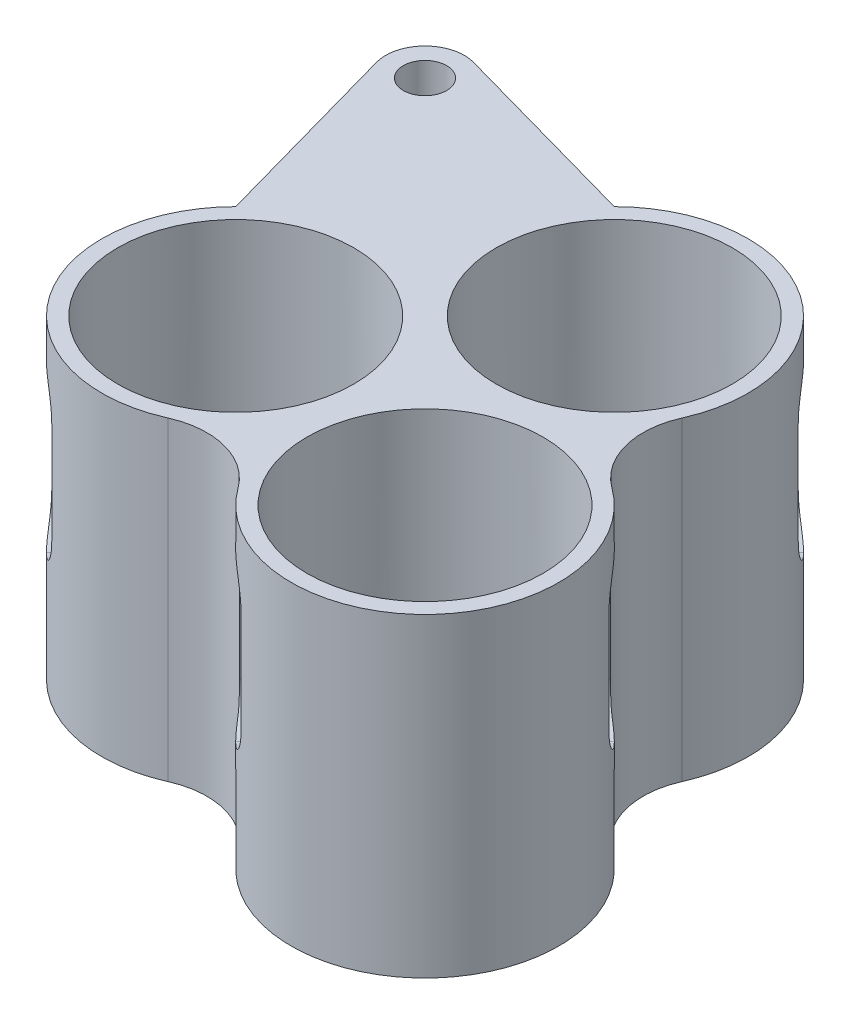
SolidWorks part; units mm, degrees
ref_plane "Front Plane" through (0, 0, 0) normal (0, 0, 1) x (1, 0, 0)
ref_plane "Top Plane" through (0, 0, 0) normal (0, 1, 0) x (1, 0, 0)
ref_plane "Right Plane" through (0, 0, 0) normal (1, 0, 0) x (0, 0, -1)
sketch "Sketch1" plane through (0, 0, 0) normal (0, 1, 0) x (1, 0, 0)
  line L1 (-15, -15) -> (15, -15)
  line L2 (-15, -15) -> (-15, 15)
  line L3 (-15, 15) -> (15, 15)
  line L4 (15, -15) -> (15, 15)
  line L5 (-15, -15) -> (15, 15) construction
  line L6 (-15, 15) -> (15, -15) construction
  point P0 (0, 0)
  dimension "D1" = 30
extrude "Boss-Extrude1" add sketch "Sketch1" along normal blind 80
sketch "Sketch2" plane through (0, 80, 0) normal (0, 1, 0) x (1, 0, 0)
  line L0 (-15, -15) -> (15, -15) construction
  line L1 (15, -15) -> (15, 15) construction
  circle A0 centre (9, -9) radius 6
  dimension "D1" = 12
extrude "Boss-Extrude2" add sketch "Sketch2" along normal blind 22
sketch "Sketch3" plane through (0, 80, 0) normal (0, 1, 0) x (1, 0, 0)
  line L2 (9, -15) -> (15, -15)
  line L4 (15, -15) -> (15, -9)
  circle A1 centre (9, -9) radius 6
  arc A4 (9, -15) -> (15, -9) centre (9, -9) ccw
  dimension "D1" = 0
extrude "Cut-Extrude1" cut sketch "Sketch3" against normal through all
sketch "Sketch4" plane through (0, 80, 0) normal (0, 1, 0) x (1, 0, 0)
  line L1 (-8.25, 11.25) -> (-1.75, 11.25) construction
  line L2 (-8.25, 11.25) -> (-8.25, 8.25)
  line L6 (-1.75, 1.75) -> (-11.25, 1.75)
  line L8 (-8.25, 8.25) -> (-11.25, 8.25)
  line L9 (-11.25, 1.75) -> (-11.25, 8.25) construction
  line L10 (-1.75, 11.25) -> (-1.75, 1.75)
  line L11 (-11.25, -1.25) -> (1.25, -1.25)
  line L12 (1.25, -1.25) -> (1.25, 11.25)
  line L13 (1.25, 11.25) -> (-1.75, 11.25) construction
  line L14 (-11.25, 1.75) -> (-11.25, -1.25) construction
  line L15 (-11.25, 8.25) -> (-11.25, 11.25) construction
  line L16 (-11.25, 11.25) -> (-8.25, 11.25) construction
  line L17 (1.25, 11.25) -> (1.25, 15)
  line L18 (15, 15) -> (-15, 15) construction
  line L19 (1.25, 15) -> (-1.75, 15)
  line L20 (-1.75, 15) -> (-1.75, 11.25)
  line L21 (-8.25, 11.25) -> (-8.25, 15)
  line L22 (-8.25, 15) -> (-11.25, 15)
  line L23 (-11.25, 15) -> (-11.25, 11.25)
  line L24 (-11.25, 11.25) -> (-15, 11.25)
  line L25 (-15, 15) -> (-15, -15) construction
  line L26 (-15, 11.25) -> (-15, 8.25)
  line L27 (-15, 8.25) -> (-11.25, 8.25)
  line L28 (-11.25, 1.75) -> (-15, 1.75)
  line L29 (-15, 1.75) -> (-15, -1.25)
  line L30 (-15, -1.25) -> (-11.25, -1.25)
  dimension "D1" = 6.5
  dimension "D2" = 3
  dimension "D3" = 3.75
extrude "Boss-Extrude3" add sketch "Sketch4" along normal blind 100
sketch "Sketch6" plane through (0, 0, 0) normal (0, -1, 0) x (1, 0, 0)
  line L1 (15, -15) -> (7, -15)
  line L2 (15, -15) -> (15, -105.5)
  line L3 (15, -105.5) -> (13, -105.5)
  line L4 (7, -15) -> (7, -99.5)
  arc A1 (7, -99.5) -> (13, -105.5) centre (7, -105.5) ccw
  dimension "D3" = 12
  dimension "D1" = 90.5
  dimension "D2" = 8
extrude "Boss-Extrude5" add sketch "Sketch6" against normal blind 2
sketch "Sketch7" plane through (0, 2, 0) normal (0, 1, 0) x (1, 0, 0)
  line L0 (7, 109.5) -> (7, 111.5) construction
  line L1 (9, 111.1569) -> (9, 108.9641)
  line L2 (5, 111.1569) -> (5, 108.9641)
  line L3 (7, 101.5) -> (7, 99.5) construction
  line L4 (15, 105.5) -> (13, 105.5)
  line L5 (15, 105.5) -> (15, 15)
  line L6 (15, 15) -> (7, 15)
  line L7 (7, 15) -> (7, 99.5) construction
  line L8 (15, 15) -> (1.25, 15) construction
  line L9 (7, 15) -> (7, 99.5)
  arc A0 (5, 111.1569) -> (7, 99.5) centre (7, 105.5) ccw
  arc A1 (13, 105.5) -> (7, 99.5) centre (7, 105.5) ccw construction
  arc A2 (5, 108.9641) -> (9, 108.9641) centre (7, 105.5) ccw
  arc A3 (13, 105.5) -> (9, 111.1569) centre (7, 105.5) ccw
  dimension "D1" = 2
  dimension "D2" = 2
extrude "Boss-Extrude6" add sketch "Sketch7" along normal offset from surface (23 mm away) 25 up to face at (3.75, 0, -38.4375)
sketch "Sketch9" plane through (0, 0, 0) normal (0, -1, 0) x (1, 0, 0)
  line L0 (15, -15) -> (7, -15) construction
  line L1 (-15, 15) -> (-132.175, 15) construction
  line L2 (-15, 15) -> (-15, 7)
  line L3 (-15, 7) -> (-126.175, 7) construction
  line L4 (-132.175, 15) -> (-132.175, 13.1746) construction
  line L5 (-136.05, 7) -> (-136.175, 7) construction
  line L6 (-128.175, 7) -> (-126.175, 7) construction
  line L7 (-126.175, 9) -> (-128.856, 9) construction
  line L8 (7, -109.5) -> (7, -111.5) construction
  line L9 (9, -111.1569) -> (5, -111.1569) construction
  line L10 (-126.175, 5) -> (-128.856, 5) construction
  line L11 (-126.175, 9) -> (-126.175, 5) construction
  line L12 (-128.7978, 8.9) -> (-126.3, 8.9)
  line L13 (-128.7978, 5.1) -> (-126.175, 5.1) construction
  line L14 (-126.175, 5.1) -> (-126.175, 7) construction
  line L15 (-126.175, 8.9) -> (-126.3, 8.9) construction
  line L16 (-132.05, 15) -> (-132.05, 13.1733)
  line L17 (-132.05, 14.0867) -> (-132.175, 14.0873) construction
  line L18 (-132.05, 15) -> (-15, 15)
  line L19 (-126.175, 5.1) -> (-126.175, 7) construction
  line L20 (-15, 7) -> (-126.175, 7)
  line L21 (-126.4838, 5.1) -> (-128.7978, 5.1)
  circle A0 centre (-132.175, 7) radius 4 construction
  arc A1 (9, -108.9641) -> (5, -108.9641) centre (7, -105.5) ccw construction
  arc A2 (-128.7978, 8.9) -> (-128.7978, 5.1) centre (-132.175, 7) ccw
  arc A4 (-126.3, 8.9) -> (-132.175, 13.1746) centre (-132.175, 7) ccw construction
  arc A6 (-126.3, 8.9) -> (-132.05, 13.1733) centre (-132.175, 7) ccw
  arc A7 (-126.4838, 5.1) -> (-126.175, 7) centre (-132.175, 7) ccw
  arc A8 (7, -99.5) -> (5, -111.1569) centre (7, -105.5) ccw construction
  dimension "D1" = 117.175
  dimension "D2" = 0.125
  dimension "D3" = 1.9
extrude "Boss-Extrude7" add sketch "Sketch9" against normal blind 25
fillet "Fillet1" radius 2 1 edges at (-126.175, 12.5, 7)
sketch "Sketch11" plane through (0, 0, 0) normal (0, -1, 0) x (1, 0, 0)
  line L0 (-126.3, 8.9) -> (-126.425, 8.9) construction
  line L2 (-126.3, 8.9) -> (-128.7978, 8.9) construction
  line L3 (-136.05, 7) -> (-136.175, 7) construction
  circle A0 centre (-132.175, 7) radius 6.0558
  arc A5 (-128.7978, 8.9) -> (-128.7978, 5.1) centre (-132.175, 7) ccw construction
extrude "Cut-Extrude2" cut sketch "Sketch11" against normal offset from surface (2.125 mm away) 0.125 up to face at (7, 2, -108.2802) offset beyond the face yes
sketch "Sketch12" plane through (-15, 0, 0) normal (-1, 0, 0) x (0, 0, 1)
  line L1 (-15, 77) -> (-1.75, 77)
  line L2 (-15, 77) -> (-15, 68.5)
  line L3 (-15, 68.5) -> (-1.75, 68.5)
  line L4 (-1.75, 77) -> (-1.75, 68.5)
  line L6 (-15, 80) -> (-15, 0) construction
  line L7 (-15, 80) -> (-1.75, 80) construction
  line L9 (-1.75, 180) -> (-1.75, 80) construction
  dimension "D1" = 8.5
  dimension "D2" = 3
extrude "Cut-Extrude4" cut sketch "Sketch12" against normal up to surface (13.25 mm away) up to face at (-1.75, 130, -8.375)
sketch "Sketch14" plane through (0, 0, 15) normal (0, 0, 1) x (1, 0, 0)
  line L0 (15, 0) -> (-136.05, 0) construction
  line L1 (-136.05, 25) -> (-136.05, 2.125) construction
  line L2 (-132.05, 0) -> (9, 0) construction
sketch "Sketch15" plane through (0, 80, 0) normal (0, 1, 0) x (1, 0, 0)
  line L4 (-11.25, 11.25) -> (-11.25, 15)
  line L5 (-11.25, 15) -> (-15, 15)
  line L6 (-15, 15) -> (-15, 11.25)
  line L7 (-15, 11.25) -> (-11.25, 11.25)
  line L8 (-11.25, 11.25) -> (-11.25, 15)
  line L9 (-11.25, 15) -> (-15, 15)
  line L10 (-15, 15) -> (-15, 11.25)
  line L11 (-15, 11.25) -> (-11.25, 11.25)
  dimension "D1" = 0
extrude "Cut-Extrude5" cut sketch "Sketch15" against normal up to next
fillet "Fillet2" radius 1 5 edges at (1.25, 130, -15) (-11.25, 128.5, -15) (-11.25, 128.5, -11.25) (-15, 128.5, -11.25) (-15, 130, 1.25)
sketch "Sketch16" plane through (0, 80, 0) normal (0, 1, 0) x (1, 0, 0)
  circle A0 centre (9, -9) radius 6
  circle A1 centre (9, -9) radius 6 construction
extrude "Cut-Extrude7" cut sketch "Sketch16" along normal up to next
sketch "Sketch17" plane through (0, 180, 0) normal (0, 1, 0) x (1, 0, 0)
  line L0 (18.7916, -9.75) -> (18.7916, -11.75) construction
  line L1 (1.25, 5.25) -> (3.7916, 5.25) construction
  line L2 (1.25, -1.25) -> (1.25, 14) construction
  line L3 (-5.25, -3.7916) -> (-5.25, -1.25) construction
  line L4 (-14, -1.25) -> (1.25, -1.25) construction
  line L6 (-5.25, -1.25) -> (1.25, -1.25) construction
  line L7 (1.25, -1.25) -> (1.25, 5.25) construction
  line L8 (-14, -1.25) -> (-14, -4.2164)
  line L9 (1.25, 14) -> (4.2164, 14)
  line L10 (-14, -1.25) -> (1.25, -1.25)
  line L11 (1.25, -1.25) -> (1.25, 14)
  circle A0 centre (18.7916, 5.25) radius 15
  circle A1 centre (-5.25, -18.7916) radius 15
  arc A2 (20.5619, -11.6576) -> (4.2164, 14) centre (18.7916, 5.25) ccw
  arc A3 (-14, -4.2164) -> (11.6576, -20.5619) centre (-5.25, -18.7916) ccw
  arc A4 (11.6576, -20.5619) -> (20.5619, -11.6576) centre (21.6032, -21.6032) cw
  dimension "D1" = 30
  dimension "D3" = 10
  dimension "D2" = 2
  dimension "D4" = 6.5
extrude "Boss-Extrude8" add sketch "Sketch17" against normal blind 40
fillet "Fillet3" radius 1 4 edges at (4.2164, 160, -14) (1.25, 160, -14) (-14, 160, 1.25) (-14, 160, 4.2164)
sketch "Sketch18" plane through (0, 140, 0) normal (0, -1, 0) x (1, 0, 0)
  circle A0 centre (-5.25, 18.7916) radius 15 construction
  circle A1 centre (-5.25, 18.7916) radius 15
  circle A2 centre (-5.25, 18.7916) radius 7.5
  dimension "D1" = 15
extrude "Boss-Extrude9" add sketch "Sketch18" against normal blind 2
sketch "Sketch19" plane through (0, 140, 0) normal (0, -1, 0) x (1, 0, 0)
  line L0 (-5.25, 26.2916) -> (-5.25, 11.2916) construction
  circle A0 centre (-5.25, 18.7916) radius 7.5 construction
ref_plane "Plane1" through (-5.25, 0, 0) normal (-1, 0, 0) x (0, 0, -1)
sketch "Sketch21" plane through (-5.25, 0, 0) normal (-1, 0, 0) x (0, 0, -1)
  line L0 (-11.2916, -142) -> (-3.7916, -154.5)
  line L1 (-26.2916, -142) -> (-11.2916, -142) construction
  line L2 (-3.7916, -154.5) -> (-3.7916, -142)
  line L3 (-33.7916, -142) -> (-3.7916, -142) construction
  line L4 (-3.7916, -142) -> (-11.2916, -142)
  line L5 (-18.7916, -1065) -> (-18.7916, 48935) construction
  line L6 (-26.2916, -140) -> (-11.2916, -140) construction
  point P14 (-18.7916, -140)
  dimension "D1" = 12.5
revolve "Revolve1" add sketch "Sketch21" angle 360 about L5
ref_plane "Plane2" through (0, 0, 0) normal (0.7071, 0, -0.7071) x (-0.7071, 0, -0.7071)
mirror "Mirror1" about plane through (0, 0, 0) normal (0.7071, 0, -0.7071) of "Revolve1", "Boss-Extrude9"
sketch "Sketch22" plane through (0, 140, 0) normal (0, -1, 0) x (1, 0, 0)
  circle A0 centre (0, 0) radius 209.0164
extrude "Cut-Extrude8" cut sketch "Sketch22" along normal through all
sketch "Sketch23" plane through (0, 180, 0) normal (0, 1, 0) x (1, 0, 0)
  line L1 (-26.7546, 5.072) -> (-4.6842, 5.072)
  line L2 (-26.7546, 5.072) -> (-26.7546, 21.2842)
  line L3 (-26.7546, 21.2842) -> (-4.6842, 21.2842)
  line L4 (-4.6842, 5.072) -> (-4.6842, 21.2842)
extrude "Cut-Extrude9" cut sketch "Sketch23" against normal through all
sketch "Sketch24" plane through (0, 180, 0) normal (0, 1, 0) x (1, 0, 0)
  line L0 (-1.75, 1.75) -> (0, 0) construction
  line L1 (0, 0) -> (39.6123, -39.6123) construction
  line L2 (-5.25, -18.7916) -> (18.7916, 5.25) construction
  line L3 (18.7916, 5.25) -> (27.5915, -27.5915) construction
  line L4 (27.5915, -27.5915) -> (-5.25, -18.7916) construction
  line L5 (-20.25, -18.7916) -> (-22.25, -18.7916) construction
  line L6 (42.5915, -27.5915) -> (44.5915, -27.5915) construction
  circle A0 centre (27.5915, -27.5915) radius 15
  circle A1 centre (18.7916, 5.25) radius 15 construction
  circle A2 centre (18.7916, 5.25) radius 15 construction
  arc A3 (13.8342, -37.5784) -> (37.5784, -13.8342) centre (27.5915, -27.5915) ccw
  circle A4 centre (-5.25, -18.7916) radius 15 construction
  arc A5 (-14.4583, -4.5015) -> (11.6576, -20.5619) centre (-5.25, -18.7916) ccw construction
  arc A6 (13.8342, -37.5784) -> (1.6707, -34.3192) centre (5.7417, -43.453) ccw
  arc A7 (37.5784, -13.8342) -> (34.3192, -1.6707) centre (43.453, -5.7417) cw
  arc A8 (20.5619, -11.6576) -> (11.6576, -20.5619) centre (21.6032, -21.6032) ccw construction
  arc A9 (20.5619, -11.6576) -> (4.5015, 14.4583) centre (18.7916, 5.25) ccw construction
  arc A10 (20.5619, -11.6576) -> (34.3192, -1.6707) centre (18.7916, 5.25) ccw
  arc A11 (20.5619, -11.6576) -> (11.6576, -20.5619) centre (21.6032, -21.6032) ccw
  arc A12 (1.6707, -34.3192) -> (11.6576, -20.5619) centre (-5.25, -18.7916) ccw
extrude "Boss-Extrude10" add sketch "Sketch24" against normal up to surface (40 mm away) up to face at (-2.677, 140, -2.677)
sketch "Sketch25" plane through (0, 140, 0) normal (0, -1, 0) x (1, 0, 0)
  circle A0 centre (27.5915, 27.5915) radius 15 construction
  circle A1 centre (27.5915, 27.5915) radius 15
  circle A2 centre (27.5915, 27.5915) radius 7.5
  circle A3 centre (-5.25, 18.7916) radius 7.5 construction
extrude "Boss-Extrude11" add sketch "Sketch25" against normal blind 2
ref_plane "Plane3" through (0, 0, 0) normal (0.7071, 0, -0.7071) x (-0.7071, 0, -0.7071)
sketch "Sketch26" plane through (0, 0, 0) normal (0.7071, 0, -0.7071) x (-0.7071, 0, -0.7071)
  line L0 (-39.0202, 126.9954) -> (-39.0202, 195.0175) construction
  line L2 (-24.0202, 142) -> (-24.0202, 154.5)
  line L3 (-24.0202, 154.5) -> (-31.5202, 142)
  line L4 (-31.5202, 142) -> (-24.0202, 142)
  line L5 (-24.0202, 142) -> (-54.0202, 142) construction
  line L7 (-24.0202, 142) -> (-24.0202, 180) construction
  line L8 (-31.5202, 142) -> (-46.5202, 142) construction
  dimension "D1" = 12.5
revolve "Revolve2" add sketch "Sketch26" angle 360 about L0
sketch "Sketch27" plane through (0, 180, 0) normal (0, 1, 0) x (1, 0, 0)
  line L0 (2.25, 14) -> (2.25, -2.25) construction
  line L1 (2.25, -2.25) -> (-14, -2.25) construction
  line L2 (2.25, -2.25) -> (2.25, 72.75)
  line L3 (2.25, 72.75) -> (-1.75, 72.75)
  line L4 (-1.75, 72.75) -> (-1.75, 1.75)
  line L5 (-1.75, 15) -> (-1.75, 1.75) construction
  line L6 (-1.75, 1.75) -> (-72.75, 1.75)
  line L7 (-72.75, 1.75) -> (-72.75, -2.25)
  line L8 (-72.75, -2.25) -> (2.25, -2.25)
  line L9 (-1.75, 1.75) -> (-15, 1.75) construction
  line L10 (3.6609, 14) -> (1.9821, 14) construction
  line L11 (-14, -1.9821) -> (-14, -3.6609) construction
  dimension "D1" = 4
  dimension "D2" = 75
extrude "Boss-Extrude12" add sketch "Sketch27" against normal up to surface (40 mm away) up to face at (0.8594, 140, 0.8594)
sketch "Sketch29" plane through (0, 0, 2.25) normal (0, 0, 1) x (1, 0, 0)
  line L0 (-72.75, 140) -> (-14, 140) construction
  line L1 (-14, 140) -> (-14, 180) construction
  line L2 (-72.75, 160) -> (-8.9096, 160) construction
  line L3 (-72.75, 140) -> (-72.75, 180) construction
  circle A0 centre (-24, 144) radius 2
  circle A1 centre (-24, 176) radius 2
  circle A2 centre (-68.75, 144) radius 2
  circle A3 centre (-68.75, 176) radius 2
  dimension "D1" = 4
  dimension "D2" = 4
  dimension "D3" = 10
  dimension "D4" = 4
extrude "Cut-Extrude10" cut sketch "Sketch29" against normal through all
sketch "Sketch30" plane through (0, 0, -1.75) normal (0, 0, -1) x (-1, 0, 0)
  line L0 (17.16, 148) -> (26.52, 148) construction
  line L1 (32.57, 148) -> (41.93, 148) construction
  line L2 (47.98, 148) -> (57.34, 148) construction
  line L3 (72.75, 140) -> (1.75, 140) construction
  line L4 (72.75, 160) -> (1.75, 160) construction
  line L5 (11.11, 148) -> (1.75, 148) construction
  line L6 (1.75, 180) -> (1.75, 140) construction
  line L7 (63.39, 148) -> (72.75, 148) construction
  line L8 (72.75, 140) -> (72.75, 180) construction
  line L9 (63.39, 172) -> (72.75, 172) construction
  line L10 (11.11, 172) -> (1.75, 172) construction
  line L11 (47.98, 172) -> (57.34, 172) construction
  line L12 (32.57, 172) -> (41.93, 172) construction
  line L13 (17.16, 172) -> (26.52, 172) construction
  circle A0 centre (14.135, 148) radius 3.025
  circle A1 centre (29.545, 148) radius 3.025
  circle A2 centre (44.955, 148) radius 3.025
  circle A3 centre (60.365, 148) radius 3.025
  circle A4 centre (60.365, 172) radius 3.025
  circle A5 centre (44.955, 172) radius 3.025
  circle A6 centre (29.545, 172) radius 3.025
  circle A7 centre (14.135, 172) radius 3.025
  dimension "D1" = 6.05
  dimension "D2" = 8
extrude "Cut-Extrude11" cut sketch "Sketch30" against normal blind 2.1
mirror "Mirror2" about plane through (0, 0, 0) normal (0.7071, 0, -0.7071) of "Cut-Extrude11", "Cut-Extrude10"
sketch "Sketch31" plane through (0, 180, 0) normal (0, 1, 0) x (1, 0, 0)
  line L0 (2.25, 14) -> (2.25, 72.75) construction
  line L1 (-77.75, 77.75) -> (2.25, 77.75)
  line L2 (-77.75, 77.75) -> (-77.75, -2.25)
  line L3 (-77.75, -2.25) -> (2.25, -2.25)
  line L4 (2.25, 77.75) -> (2.25, -2.25)
  line L5 (-72.75, -2.25) -> (-14, -2.25) construction
  dimension "D1" = 80
extrude "Cut-Extrude12" cut sketch "Sketch31" against normal through all both and the other way through all
sketch "Sketch32" plane through (0, 180, 0) normal (0, 1, 0) x (1, 0, 0)
  line L1 (-14, -2.25) -> (2.25, -2.25)
  line L2 (-14, -2.25) -> (-14, 9)
  line L3 (-9, 14) -> (2.25, 14)
  line L4 (2.25, -2.25) -> (2.25, 14)
  arc A0 (-14, 9) -> (-9, 14) centre (-9, 9) cw
  dimension "D1" = 5
extrude "Boss-Extrude13" add sketch "Sketch32" against normal offset from surface (190 mm away) 150 up to face at (5.7965, 140, 5.7965) offset beyond the face yes
sketch "Sketch33" plane through (0, 0, 2.25) normal (0, 0, 1) x (1, 0, 0)
  line L0 (-22.25, 140) -> (1.6707, 140) construction
  line L1 (-58.8107, 140) -> (17.082, 140)
  line L2 (-58.8107, 140) -> (-58.8107, -10.8319)
  line L3 (-58.8107, -10.8319) -> (17.082, -10.8319)
  line L4 (17.082, 140) -> (17.082, -10.8319)
extrude "Cut-Extrude13" cut sketch "Sketch33" against normal through all both
sketch "Sketch35" plane through (0, 180, 0) normal (0, 1, 0) x (1, 0, 0)
  line L0 (-18.6785, -8.1785) -> (8.3498, 18.8498)
  line L1 (8.3498, 18.8498) -> (-21.2132, 21.2132)
  line L2 (-21.2132, 21.2132) -> (-18.6785, -8.1785)
  line L3 (0, 0) -> (-21.2132, 21.2132) construction
  arc A0 (-14.4583, -4.5015) -> (1.6707, -34.3192) centre (-5.25, -18.7916) ccw construction
  arc A1 (34.3192, -1.6707) -> (4.5015, 14.4583) centre (18.7916, 5.25) ccw construction
  arc A2 (-9, 14) -> (-14, 9) centre (-9, 9) ccw construction
  point P14 (-12.5355, 12.5355)
  dimension "D1" = 30
extrude "Cut-Extrude14" cut sketch "Sketch35" against normal through all
sketch "Sketch34" plane through (0, 180, 0) normal (0, 1, 0) x (1, 0, 0)
  line L1 (-14, -3.5) -> (3.5, 14)
  line L2 (-17.2708, -6.7708) -> (-24.2076, 18.0461)
  line L3 (-18.0461, 24.2076) -> (6.7708, 17.2708)
  line L4 (-21.7962, -11.2962) -> (10.7464, 21.2464) construction
  line L5 (-14, -3.5) -> (3.5, 14) construction
  line L6 (-5.25, 5.25) -> (0, 0) construction
  line L7 (-19.3921, 19.3921) -> (-5.25, 5.25) construction
  line L8 (-14, -3.5) -> (-14, -3.6609) construction
  line L9 (3.6609, 14) -> (3.5, 14) construction
  line L10 (-14, -3.5) -> (-14, -3.6609)
  line L11 (3.6609, 14) -> (3.5, 14)
  circle A0 centre (-19.3921, 19.3921) radius 2.75
  arc A1 (-24.2076, 18.0461) -> (-18.0461, 24.2076) centre (-19.3921, 19.3921) cw
  arc A2 (34.3192, -1.6707) -> (4.5015, 14.4583) centre (18.7916, 5.25) ccw construction
  arc A3 (-14.4583, -4.5015) -> (-14, -3.6609) centre (-15, -3.6609) ccw construction
  arc A4 (-14.4583, -4.5015) -> (1.6707, -34.3192) centre (-5.25, -18.7916) ccw construction
  arc A5 (3.6609, 14) -> (4.5015, 14.4583) centre (3.6609, 15) ccw construction
  arc A6 (-14.4583, -4.5015) -> (-14, -3.6609) centre (-15, -3.6609) ccw
  arc A7 (-14.4583, -4.5015) -> (-17.2708, -6.7708) centre (-5.25, -18.7916) ccw
  arc A8 (6.7708, 17.2708) -> (4.5015, 14.4583) centre (18.7916, 5.25) ccw
  arc A9 (3.6609, 14) -> (4.5015, 14.4583) centre (3.6609, 15) ccw
  point P7 (7.8738, 18.2808)
  dimension "D1" = 5.5
  dimension "D2" = 5
  dimension "D3" = 20
extrude "Boss-Extrude14" add sketch "Sketch34" against normal blind 4
chamfer "Chamfer1" distance 12 angle 45 1 edges at (-5.25, 176, -5.25)
sketch "Sketch36" plane through (0, 0, 0) normal (0.7071, 0, -0.7071) x (-0.7071, 0, -0.7071)
  line L0 (-9.5754, 180) -> (25.8239, 180) construction
  line L1 (-13.5754, 154) -> (-5.5754, 154)
  line L2 (-13.5754, 154) -> (-13.5754, 175)
  line L3 (-13.5754, 175) -> (-5.5754, 175)
  line L4 (-5.5754, 154) -> (-5.5754, 175)
  line L5 (7.4246, 180) -> (-25.4487, 180) construction
  line L6 (5.4246, 180) -> (-24.5754, 180) construction
  line L8 (-25.4487, 140) -> (7.4246, 140) construction
  line L9 (-39.0202, 180) -> (-28.1443, 180) construction
  line L10 (-36.3542, 180) -> (-56.0202, 180) construction
  line L11 (-25.4487, 180) -> (-36.3542, 180) construction
  line L12 (-24.0202, 180) -> (-54.0202, 180) construction
  line L14 (-43.0202, 175) -> (-35.0202, 175)
  line L15 (-43.0202, 175) -> (-43.0202, 154)
  line L16 (-43.0202, 154) -> (-35.0202, 154)
  line L17 (-35.0202, 175) -> (-35.0202, 154)
  point P13 (-9.5754, 175)
  point P22 (-39.0202, 175)
  dimension "D1" = 5
  dimension "D2" = 14
  dimension "D3" = 8
extrude "Cut-Extrude15" cut sketch "Sketch36" against normal through all both and the other way through all
fillet "Fillet4" radius 4 20 edges at (-19.0313, 175, 26.9161) (3.9424, 175, 3.9424) (-13.3745, 175, 32.573) (9.5992, 175, 9.5992) (-18.9212, 154, 26.806) (3.9424, 154, 3.9424) (-13.2644, 154, 32.4628) (9.5992, 154, 9.5992) (32.573, 175, -13.3745) (26.9161, 175, -19.0313) (26.806, 154, -18.9212) (32.4628, 154, -13.2644) (35.6574, 154, 13.8687) (13.8687, 154, 35.6574) (19.5771, 154, 41.2627) (41.2627, 154, 19.5771) (13.7585, 175, 35.7676) (35.7676, 175, 13.7585) (19.467, 175, 41.3728) (41.3728, 175, 19.467)
